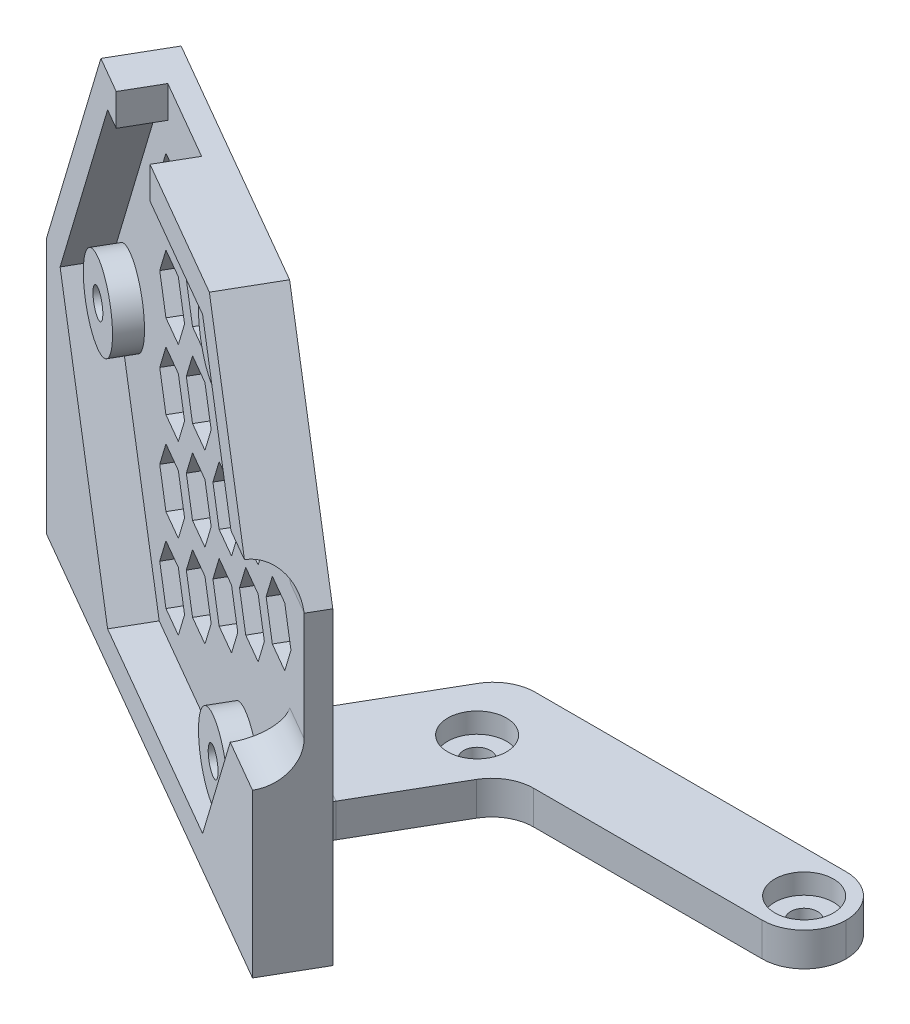
SolidWorks part; units mm, degrees
ref_plane "Plan de face" through (0, 0, 0) normal (0, 0, 1) x (1, 0, 0)
ref_plane "Plan de dessus" through (0, 0, 0) normal (0, 1, 0) x (1, 0, 0)
ref_plane "Plan de droite" through (0, 0, 0) normal (1, 0, 0) x (0, 0, -1)
sketch "Esquisse1" plane through (0, 0, 0) normal (0, -1, 0) x (1, 0, 0)
  line L0 (-2.2542, -612.3906) -> (-1.4342, -613.8109) construction
  line L1 (-1.4342, -613.8109) -> (24.5466, -598.8109) construction
  line L2 (24.5466, -598.8109) -> (23.7266, -597.3906) construction
  line L3 (23.7266, -597.3906) -> (-2.2542, -612.3906) construction
  circle A0 centre (30.4658, -623.4307) radius 1.7
  circle A1 centre (66.5558, -626.3007) radius 1.7
  circle A3 centre (5.084, -609.1007) radius 5
  point P8 (0, 0)
ref_plane "Plan1" through (265.4294, 0, -459.7371) normal (-0.5, 0, 0.866) x (0.866, 0, 0.5)
ref_plane "Plan2" through (266.8244, 0, -462.1533) normal (-0.5, 0, 0.866) x (0.866, 0, 0.5)
sketch "Esquisse2" plane through (684.3819, 0, -221.0764) normal (0.5, 0, -0.866) x (-0.866, 0, -0.5)
  line L19 (775.3014, 56.5615) -> (775.3014, 4.6) construction
  line L20 (776.9614, 58.1615) -> (776.9614, 56.5615) construction
  line L21 (787.9614, 56.5615) -> (776.9614, 56.5615) construction
  line L22 (787.9614, 58.1615) -> (787.9614, 56.5615) construction
  line L23 (787.9614, 58.1615) -> (776.9614, 58.1615) construction
  line L24 (748.1881, 35.5808) -> (760.3014, 56.5615) construction
  line L25 (760.3014, 4.6) -> (748.1881, 25.5808) construction
  line L26 (790.3014, 4.6) -> (760.3014, 4.6) construction
  line L27 (805.3014, 30.5808) -> (790.3014, 4.6) construction
  line L28 (790.3014, 56.5615) -> (805.3014, 30.5808) construction
  line L29 (760.3014, 56.5615) -> (790.3014, 56.5615) construction
  line L30 (748.1881, 35.5808) -> (748.1881, 25.5808) construction
  line L31 (790.3014, 0) -> (760.3014, 0) construction
  point P1 (787.9614, 57.3615)
  point P2 (790.3014, 55.3074)
  point P3 (790.3014, 65.6843)
  point P4 (775.3014, 3.3459)
  point P8 (790.3014, 55.9615)
  point P9 (790.3014, 4)
  point P10 (776.9614, 55.9615)
  point P11 (787.9614, 55.9615)
  dimension "D1" = 30
  dimension "D2" = 20.9808
  dimension "D3" = 10
  dimension "D4" = 20.9808
  dimension "D5" = 30
  dimension "D6" = 30
  dimension "D7" = 30
  dimension "D8" = 51.9615
  dimension "D9" = 120
  dimension "D10" = 120
  dimension "D11" = 120
  dimension "D12" = 120
  dimension "D13" = 120
  dimension "D14" = 150
  dimension "D15" = 150
  dimension "D16" = 15
  dimension "D17" = 2.34
  dimension "D18" = 11
  dimension "D19" = 1.6
  dimension "D20" = 11
  dimension "D21" = 1.6
  dimension "D22" = 90
  dimension "D23" = 90
  dimension "D24" = 0
  dimension "D25" = 4.6
  dimension "D26" = 0
  dimension "D27" = 0
sketch "Esquisse3" plane through (266.8244, 0, -462.1533) normal (-0.5, 0, 0.866) x (0.866, 0, 0.5)
  line L7 (-275.4916, 61.1615) -> (-310.8033, 61.1615)
  line L8 (-310.8033, 61.1615) -> (-328.4591, 30.5808)
  line L9 (-328.4591, 30.5808) -> (-310.8033, 0)
  line L10 (-310.8033, 0) -> (-275.4916, 0)
  line L11 (-275.4916, 0) -> (-261.4342, 24.3482)
  line L12 (-261.4342, 24.3482) -> (-261.4342, 36.8133)
  line L13 (-261.4342, 36.8133) -> (-275.4916, 61.1615)
  line L14 (-277.6856, 57.3615) -> (-308.6093, 57.3615)
  line L15 (-265.2342, 35.7951) -> (-277.6856, 57.3615)
  line L16 (-265.2342, 25.3664) -> (-265.2342, 35.7951)
  line L17 (-277.6856, 3.8) -> (-265.2342, 25.3664)
  line L18 (-308.6093, 3.8) -> (-277.6856, 3.8)
  line L19 (-324.0712, 30.5808) -> (-308.6093, 3.8)
  line L20 (-308.6093, 57.3615) -> (-324.0712, 30.5808)
  line L21 (-277.6856, 57.3615) -> (-308.6093, 57.3615)
  line L22 (-265.2342, 35.7951) -> (-277.6856, 57.3615)
  line L23 (-265.2342, 25.3664) -> (-265.2342, 35.7951)
  line L24 (-277.6856, 3.8) -> (-265.2342, 25.3664)
  line L25 (-308.6093, 3.8) -> (-277.6856, 3.8)
  line L26 (-324.0712, 30.5808) -> (-308.6093, 3.8)
  line L27 (-308.6093, 57.3615) -> (-324.0712, 30.5808)
  line L28 (28.092, 0) -> (-28.092, 0) construction
  dimension "D2" = 0
  dimension "D1" = 0.8
extrude "Boss.-Extru.1" add sketch "Esquisse3" along normal blind 4.5
sketch "Esquisse4" plane through (266.8244, 0, -462.1533) normal (-0.5, 0, 0.866) x (0.866, 0, 0.5)
  line L0 (-310.8033, 61.1615) -> (-275.4916, 61.1615)
  line L1 (-275.4916, 61.1615) -> (-261.4342, 36.8133)
  line L2 (-261.4342, 36.8133) -> (-261.4342, 24.3482)
  line L3 (-261.4342, 24.3482) -> (-275.4916, 0)
  line L4 (-275.4916, 0) -> (-310.8033, 0)
  line L5 (-310.8033, 0) -> (-328.4591, 30.5808)
  line L6 (-328.4591, 30.5808) -> (-310.8033, 61.1615)
extrude "Boss.-Extru.2" add sketch "Esquisse4" against normal blind 2.5
sketch "Esquisse5" plane through (266.8244, 0, -462.1533) normal (-0.5, 0, 0.866) x (0.866, 0, 0.5)
  line L0 (-305.8075, 57.3615) -> (-305.8075, 61.1615)
  line L1 (-305.8075, 58.1615) -> (-305.8075, 56.5615) construction
  line L2 (-275.4916, 61.1615) -> (-310.8033, 61.1615) construction
  line L3 (-305.8075, 61.1615) -> (-294.8075, 61.1615)
  line L4 (-294.8075, 61.1615) -> (-294.8075, 57.3615)
  line L5 (-294.8075, 58.1615) -> (-294.8075, 56.5615) construction
  line L6 (-294.8075, 57.3615) -> (-305.8075, 57.3615)
extrude "Enlèv. mat.-Extru.1" cut sketch "Esquisse5" along normal up to next
sketch "Esquisse6" plane through (266.8244, 0, -462.1533) normal (-0.5, 0, 0.866) x (0.866, 0, 0.5)
  line L0 (-293.1475, 30.5808) -> (-280.6475, 52.2314) construction
  line L1 (-293.1475, 56.5615) -> (-293.1475, 4.6) construction
  line L2 (-293.1475, 30.5808) -> (-280.6475, 8.9301) construction
  line L3 (-293.1475, 30.5808) -> (-318.1475, 30.5808) construction
  circle A0 centre (-280.6475, 52.2314) radius 4.75
  circle A1 centre (-280.6475, 8.9301) radius 4.75
  circle A2 centre (-318.1475, 30.5808) radius 4.75
  dimension "D6" = 9.5
  dimension "D7" = 9.5
  dimension "D8" = 9.5
  dimension "D1" = 25
  dimension "D2" = 25
  dimension "D3" = 25
  dimension "D4" = 120
  dimension "D5" = 120
extrude "Boss.-Extru.3" add sketch "Esquisse6" along normal up to surface (2.79 mm away) up to plane "Plan1"
sketch "Esquisse7" plane through (266.8244, 0, -462.1533) normal (-0.5, 0, 0.866) x (0.866, 0, 0.5)
  line L0 (-328.4591, 30.5808) -> (-328.4591, 0)
  line L1 (-328.4591, 0) -> (-310.8033, 0)
  line L2 (-310.8033, 0) -> (-328.4591, 30.5808)
  line L3 (-275.4916, 0) -> (-261.4342, 24.3482)
  line L4 (-261.4342, 24.3482) -> (-261.4342, 0)
  line L5 (-261.4342, 0) -> (-275.4916, 0)
  point P9 (-261.4342, -0.8)
  point P11 (-328.4591, -0.8)
  point P12 (-310.8033, -0.864)
  point P13 (-310.8171, -0.864)
  point P14 (-313.7365, -0.5663)
  point P15 (-311.7574, -0.8)
  point P16 (-311.2281, -1.1617)
  point P17 (-310.8033, -0.8)
  dimension "D2" = 14.0574
extrude "Boss.-Extru.4" add sketch "Esquisse7" along normal up to surface (4.5 mm away) and the other way up to surface (2.5 mm away) up to face at (11.8741, 36.9543, -604.1528) other way up to face at (17.6795, 30.5808, -608.8839)
hole_wizard "Dégagement M31" positions "Esquisse9" profile "Esquisse10" hole size "M3" standard "Ansi Metric"
sketch "Esquisse9" plane through (265.4294, 0, -459.7371) normal (-0.5, 0, 0.866) x (0.866, 0, 0.5)
  point P0 (-318.1475, 30.5808)
  point P3 (-280.6475, 52.2314)
  point P6 (-280.6475, 8.9301)
sketch "Esquisse10" plane through (-10.0944, 30.5808, -618.8109) normal (0, 1, 0) x (0.866, 0, 0.5)
  line L0 (0, 0) -> (0, 3.9614)
  line L1 (0, 3.9614) -> (1.6, 3)
  line L2 (1.6, 3) -> (1.6, 0)
  line L5 (1.6, 0) -> (0, 0)
  line L10 (0, 3.9614) -> (-1.6, 3) construction
  line L11 (0, -6.35) -> (0, 107.95) construction
  dimension "Diamètre du perçage" = 3.2
  dimension "Profondeur du perçage" = 3
  dimension "Angle de pointe" = 118
sketch "Esquisse11" plane through (142.9907, 0, -533.6487) normal (-0.5, 0, 0.866) x (0.866, 0, 0.5)
  line L0 (-162.8167, 56.5615) -> (-151.8167, 56.5615) construction
  line L1 (-159.3847, 53.5615) -> (-163.4247, 53.5615)
  line L2 (-163.4247, 53.5615) -> (-165.4447, 50.0628)
  line L3 (-165.4447, 50.0628) -> (-163.4247, 46.564)
  line L4 (-163.4247, 46.564) -> (-159.3847, 46.564)
  line L5 (-159.3847, 46.564) -> (-157.3647, 50.0628)
  line L6 (-157.3647, 50.0628) -> (-159.3847, 53.5615)
  line L7 (-165.1567, 56.5615) -> (-180.1567, 30.5808) construction
  line L8 (-150.7266, 41.5653) -> (-148.7066, 45.064)
  line L9 (-148.7066, 45.064) -> (-150.7266, 48.5628)
  line L10 (-150.7266, 48.5628) -> (-154.7666, 48.5628)
  line L11 (-154.7666, 48.5628) -> (-156.7866, 45.064)
  line L12 (-156.7866, 45.064) -> (-154.7666, 41.5653)
  line L13 (-154.7666, 41.5653) -> (-150.7266, 41.5653)
  line L14 (-142.0685, 36.5666) -> (-140.0485, 40.0653)
  line L15 (-140.0485, 40.0653) -> (-142.0685, 43.564)
  line L16 (-142.0685, 43.564) -> (-146.1085, 43.564)
  line L17 (-146.1085, 43.564) -> (-148.1285, 40.0653)
  line L18 (-148.1285, 40.0653) -> (-146.1085, 36.5666)
  line L19 (-146.1085, 36.5666) -> (-142.0685, 36.5666)
  line L20 (-133.4104, 31.5678) -> (-131.3904, 35.0666)
  line L21 (-131.3904, 35.0666) -> (-133.4104, 38.5653)
  line L22 (-133.4104, 38.5653) -> (-137.4504, 38.5653)
  line L23 (-137.4504, 38.5653) -> (-139.4704, 35.0666)
  line L24 (-139.4704, 35.0666) -> (-137.4504, 31.5678)
  line L25 (-137.4504, 31.5678) -> (-133.4104, 31.5678)
  line L26 (-124.7524, 26.5691) -> (-122.7324, 30.0678)
  line L27 (-122.7324, 30.0678) -> (-124.7524, 33.5666)
  line L28 (-124.7524, 33.5666) -> (-128.7924, 33.5666)
  line L29 (-128.7924, 33.5666) -> (-130.8124, 30.0678)
  line L30 (-130.8124, 30.0678) -> (-128.7924, 26.5691)
  line L31 (-128.7924, 26.5691) -> (-124.7524, 26.5691)
  line L32 (-159.3847, 26.5691) -> (-157.3647, 30.0678)
  line L33 (-157.3647, 30.0678) -> (-159.3847, 33.5666)
  line L34 (-159.3847, 33.5666) -> (-163.4247, 33.5666)
  line L35 (-163.4247, 33.5666) -> (-165.4447, 30.0678)
  line L36 (-165.4447, 30.0678) -> (-163.4247, 26.5691)
  line L37 (-163.4247, 26.5691) -> (-159.3847, 26.5691)
  line L38 (-150.7266, 21.5703) -> (-148.7066, 25.0691)
  line L39 (-148.7066, 25.0691) -> (-150.7266, 28.5678)
  line L40 (-150.7266, 28.5678) -> (-154.7666, 28.5678)
  line L41 (-154.7666, 28.5678) -> (-156.7866, 25.0691)
  line L42 (-156.7866, 25.0691) -> (-154.7666, 21.5703)
  line L43 (-154.7666, 21.5703) -> (-150.7266, 21.5703)
  line L44 (-142.0685, 16.5716) -> (-140.0485, 20.0703)
  line L45 (-140.0485, 20.0703) -> (-142.0685, 23.5691)
  line L46 (-142.0685, 23.5691) -> (-146.1085, 23.5691)
  line L47 (-146.1085, 23.5691) -> (-148.1285, 20.0703)
  line L48 (-148.1285, 20.0703) -> (-146.1085, 16.5716)
  line L49 (-146.1085, 16.5716) -> (-142.0685, 16.5716)
  line L50 (-159.3847, 6.5741) -> (-157.3647, 10.0728)
  line L51 (-157.3647, 10.0728) -> (-159.3847, 13.5716)
  line L52 (-159.3847, 13.5716) -> (-163.4247, 13.5716)
  line L53 (-163.4247, 13.5716) -> (-165.4447, 10.0728)
  line L54 (-165.4447, 10.0728) -> (-163.4247, 6.5741)
  line L55 (-163.4247, 6.5741) -> (-159.3847, 6.5741)
  line L56 (-150.7266, 38.5653) -> (-154.7666, 38.5653)
  line L57 (-159.3847, 43.564) -> (-163.4247, 43.564)
  line L58 (-163.4247, 43.564) -> (-165.4447, 40.0653)
  line L59 (-165.4447, 40.0653) -> (-163.4247, 36.5666)
  line L60 (-163.4247, 36.5666) -> (-159.3847, 36.5666)
  line L61 (-159.3847, 36.5666) -> (-157.3647, 40.0653)
  line L62 (-157.3647, 40.0653) -> (-159.3847, 43.564)
  line L63 (-154.7666, 38.5653) -> (-156.7866, 35.0666)
  line L64 (-156.7866, 35.0666) -> (-154.7666, 31.5678)
  line L65 (-154.7666, 31.5678) -> (-150.7266, 31.5678)
  line L66 (-150.7266, 31.5678) -> (-148.7066, 35.0666)
  line L67 (-148.7066, 35.0666) -> (-150.7266, 38.5653)
  line L68 (-142.0685, 33.5666) -> (-146.1085, 33.5666)
  line L69 (-146.1085, 33.5666) -> (-148.1285, 30.0678)
  line L70 (-148.1285, 30.0678) -> (-146.1085, 26.5691)
  line L71 (-146.1085, 26.5691) -> (-142.0685, 26.5691)
  line L72 (-142.0685, 26.5691) -> (-140.0485, 30.0678)
  line L73 (-140.0485, 30.0678) -> (-142.0685, 33.5666)
  line L74 (-133.4104, 28.5678) -> (-137.4504, 28.5678)
  line L75 (-137.4504, 28.5678) -> (-139.4704, 25.0691)
  line L76 (-139.4704, 25.0691) -> (-137.4504, 21.5703)
  line L77 (-137.4504, 21.5703) -> (-133.4104, 21.5703)
  line L78 (-133.4104, 21.5703) -> (-131.3904, 25.0691)
  line L79 (-131.3904, 25.0691) -> (-133.4104, 28.5678)
  line L80 (-159.3847, 23.5691) -> (-163.4247, 23.5691)
  line L81 (-163.4247, 23.5691) -> (-165.4447, 20.0703)
  line L82 (-165.4447, 20.0703) -> (-163.4247, 16.5716)
  line L83 (-163.4247, 16.5716) -> (-159.3847, 16.5716)
  line L84 (-159.3847, 16.5716) -> (-157.3647, 20.0703)
  line L85 (-157.3647, 20.0703) -> (-159.3847, 23.5691)
  line L86 (-150.7266, 18.5703) -> (-154.7666, 18.5703)
  line L87 (-154.7666, 18.5703) -> (-156.7866, 15.0716)
  line L88 (-156.7866, 15.0716) -> (-154.7666, 11.5728)
  line L89 (-154.7666, 11.5728) -> (-150.7266, 11.5728)
  line L90 (-150.7266, 11.5728) -> (-148.7066, 15.0716)
  line L91 (-148.7066, 15.0716) -> (-150.7266, 18.5703)
  circle A0 centre (-161.4047, 50.0628) radius 3.4987 construction
  circle A1 centre (-161.4047, 40.0653) radius 3.4987 construction
  circle A2 centre (-152.7466, 35.0666) radius 3.4987 construction
  circle A3 centre (-144.0885, 30.0678) radius 3.4987 construction
  circle A4 centre (-135.4304, 25.0691) radius 3.4987 construction
  circle A5 centre (-161.4047, 20.0703) radius 3.4987 construction
  circle A6 centre (-152.7466, 15.0716) radius 3.4987 construction
  point P9 (-144.8696, 29.3928)
  point P109 (-161.4047, 26.5691)
  dimension "D1" = 4.04
  dimension "D2" = 3
  dimension "D3" = 3
  dimension "D6" = 4.04
  dimension "D7" = 3
  dimension "D8" = 3
  dimension "D9" = 3
  dimension "D11" = 3
  dimension "D12" = 3
  dimension "D14" = 3
  dimension "D15" = 3
  dimension "D17" = 3
  dimension "D18" = 3
  dimension "D4" = 5
  dimension "D5" = 2
  dimension "D16" = 2
  dimension "D10" = 4
  dimension "D13" = 2
extrude "Enlèv. mat.-Extru.2" cut sketch "Esquisse11" against normal through all
ref_plane "USB-C" through (-229.6996, 0, -132.6171) normal (-0.866, 0, -0.5) x (-0.5, 0, 0.866)
sketch "Esquisse12" plane through (-229.6996, 0, -132.6171) normal (-0.866, 0, -0.5) x (-0.5, 0, 0.866)
  line L0 (-529.1487, 36.8664) -> (-529.1487, 23.8664) construction
  line L1 (-524.6487, 36.8664) -> (-524.6487, 23.8664)
  line L2 (-533.6487, 36.8664) -> (-533.6487, 23.8664)
  line L3 (-533.6487, 56.5615) -> (-533.6487, 30.5808) construction
  line L4 (-533.6487, 30.5808) -> (-533.6487, 4.6) construction
  line L5 (-533.6487, 25.3664) -> (-533.6487, 35.7951) construction
  arc A0 (-524.6487, 36.8664) -> (-533.6487, 36.8664) centre (-529.1487, 36.8664) ccw
  arc A1 (-533.6487, 23.8664) -> (-524.6487, 23.8664) centre (-529.1487, 23.8664) ccw
  point P2 (-529.1487, 30.3664)
  point P11 (-538.1487, 29.9442)
  point P13 (-536.779, 30.6693)
  point P14 (-536.6662, 31.0521)
  point P15 (-527.7038, 30.2304)
  dimension "D6" = 1.5
  dimension "D1" = 13
  dimension "D2" = 9
  dimension "D3" = 0
  dimension "D4" = 9
  dimension "D5" = 4.5
extrude "Enlèv. mat.-Extru.3" cut sketch "Esquisse12" against normal blind 4 and the other way blind 4
sketch "Esquisse15" plane through (0, 0, 0) normal (0, 1, 0) x (1, 0, 0)
  line L0 (26.3829, 603.859) -> (36.4529, 621.3007)
  line L1 (36.4529, 621.3007) -> (71.5558, 621.3007)
  line L2 (71.5558, 621.3007) -> (71.5558, 631.3007)
  line L3 (71.5558, 631.3007) -> (26.638, 631.3007)
  line L4 (26.638, 631.3007) -> (14.6916, 610.609)
  line L5 (29.4916, 602.0642) -> (-1.0892, 619.72) construction
  line L6 (14.6916, 610.609) -> (26.3829, 603.859)
  point P9 (0, 0)
  point P10 (32.0412, 605.7806)
  dimension "D1" = 5
  dimension "D2" = 90
  dimension "D3" = 90
  dimension "D4" = 120
  dimension "D5" = 120
  dimension "D6" = 90
  dimension "D7" = 90
  dimension "D8" = 5
  dimension "D9" = 5
  dimension "D10" = 13.5
  dimension "D11" = 6.25
  dimension "D12" = 7.25
extrude "Boss.-Extru.6" add sketch "Esquisse15" along normal blind 4
hole_wizard "Chambrage pour vis à tête ronde bombée M32" positions "Esquisse16" profile "Esquisse17" counterbore size "M3" standard "Ansi Metric" end condition through all
sketch "Esquisse16" plane through (0, 4, 0) normal (0, 1, 0) x (1, 0, 0)
  point P0 (30.4658, 623.4307)
  point P3 (66.5558, 626.3007)
sketch "Esquisse17" plane through (30.4658, 4, -623.4307) normal (1, 0, 0) x (0, 0, 1)
  line L0 (0, 0) -> (0, 4)
  line L1 (0, 4) -> (1.6, 4)
  line L3 (1.6, 4) -> (1.6, 2.4)
  line L4 (1.6, 2.4) -> (3.5, 2.4)
  line L5 (3.5, 2.4) -> (3.5, 0)
  line L7 (3.5, 0) -> (0, 0)
  line L11 (0, -6.35) -> (0, 107.95) construction
  dimension "Diamètre du perçage jusqu'au prochain" = 3.2
  dimension "Profondeur du perçage jusqu'au prochain" = 4
  dimension "Diamètre du chambrage" = 7
  dimension "Profondeur du chambrage" = 2.4
fillet "Congé2" radius 5 7 edges at (26.3829, 2, -603.859) (20.5373, 4, -607.234) (14.6916, 2, -610.609) (26.638, 2, -631.3007) (71.5558, 2, -631.3007) (71.5558, 2, -621.3007) (36.4529, 2, -621.3007)
